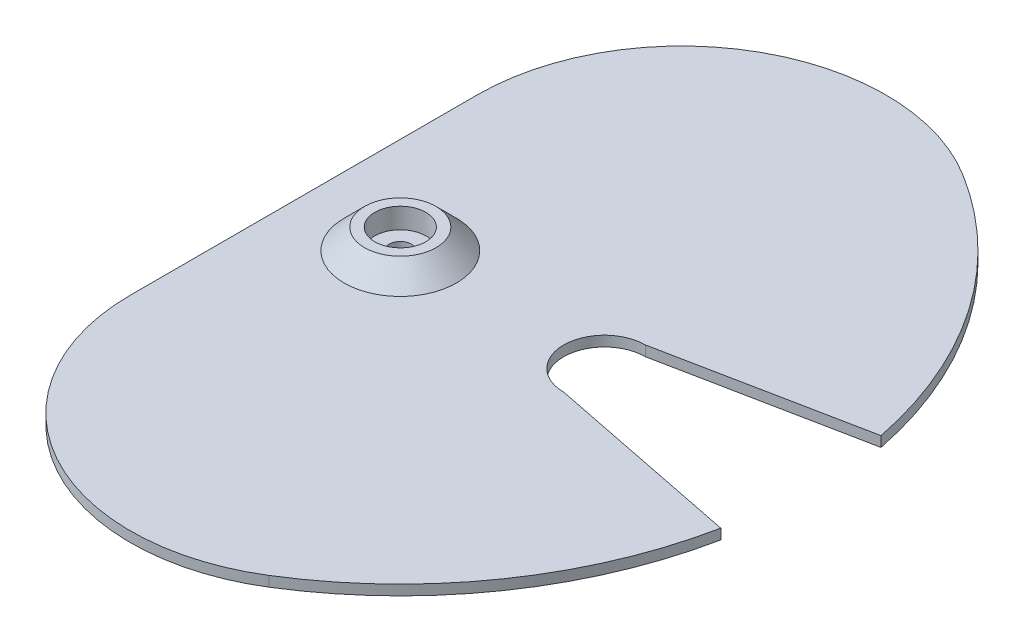
SolidWorks part; units mm, degrees
ref_plane "Plano frontal" through (0, 0, 0) normal (0, 0, 1) x (1, 0, 0)
ref_plane "Plano superior" through (0, 0, 0) normal (0, 1, 0) x (1, 0, 0)
ref_plane "Plano direito" through (0, 0, 0) normal (1, 0, 0) x (0, 0, -1)
sketch "Esboço1" plane through (0, 0, 0) normal (0, 1, 0) x (1, 0, 0)
  circle A0 centre (0, 0) radius 40
  dimension "D1" = 80
extrude "Ressalto-extrusão1" add sketch "Esboço1" along normal blind 1
sketch "Esboço2" plane through (0, 1, 0) normal (0, 1, 0) x (1, 0, 0)
  line L0 (0, 41.9322) -> (0, -42.8834) construction
  line L1 (43.2797, 0) -> (-44.548, 0) construction
  line L2 (20, 4) -> (40, 8)
  line L3 (20, -4) -> (40, -8)
  circle A0 centre (20, 0) radius 4
  circle A1 centre (0, 0) radius 40 construction
  circle A2 centre (40, 0) radius 8
  point P41 (0, 0)
  circle M2 centre (0, 0) radius 40
  dimension "D1" = 8
  dimension "D2" = 20
  dimension "D3" = 40
  dimension "D4" = 16
sketch "Esboço3" plane through (0, 1, 0) normal (0, 1, 0) x (1, 0, 0)
  circle A0 centre (0, 0) radius 3.5
  dimension "D1" = 7
extrude "Ressalto-extrusão2" add sketch "Esboço3" along normal blind 2
sketch "Esboço4" plane through (0, 3, 0) normal (0, 1, 0) x (1, 0, 0)
  circle A0 centre (0, 0) radius 2.5
  dimension "D1" = 5
extrude "Corte-extrusão2" cut sketch "Esboço4" against normal blind 2 contours A0
chamfer "Chanfro1" distance 2 angle 45 1 edges at (0, 1, 3.5)
sketch "Esboço6" plane through (0, 1, 0) normal (0, 1, 0) x (1, 0, 0)
  circle A0 centre (0, 0) radius 1.1
  dimension "D1" = 2.2
extrude "Corte-extrusão4" cut sketch "Esboço6" against normal blind 3
extrude "Corte-extrusão5" cut sketch "Esboço2" against normal blind 3 contours L2 A2 L3 M2 | A2 L2 A0 L3 | A0 M2 region at (28.4073, 1, 0) region at (20, 1, 0) region at (36.4545, 1, 0)
sketch "Esboço7" plane through (0, 1, 0) normal (0, 1, 0) x (1, 0, 0)
  line L0 (-9.4402, 38.8701) -> (-9.4402, -38.8701)
  line L1 (-9.4402, -38.8701) -> (-47.7479, -38.8701)
  line L2 (-47.7479, -38.8701) -> (-47.7479, 38.8701)
  line L3 (-47.7479, 38.8701) -> (-9.4402, 38.8701)
  arc A0 (39.2232, 7.8446) -> (39.2232, -7.8446) centre (0, 0) ccw construction
extrude "Corte-extrusão6" cut sketch "Esboço7" against normal blind 3
fillet "Filete1" radius 20 1 edges at (-9.4402, 0.5, -38.8701) type face fillet first side face at (18.1975, 0.5, -28.5428) second side face at (-9.4402, 0.5, 0)
fillet "Filete2" radius 20 1 edges at (-9.4402, 0.5, 38.8701) type face fillet first side face at (-9.4402, 0.5, 10.9425) second side face at (18.1975, 0.5, 28.5428)
